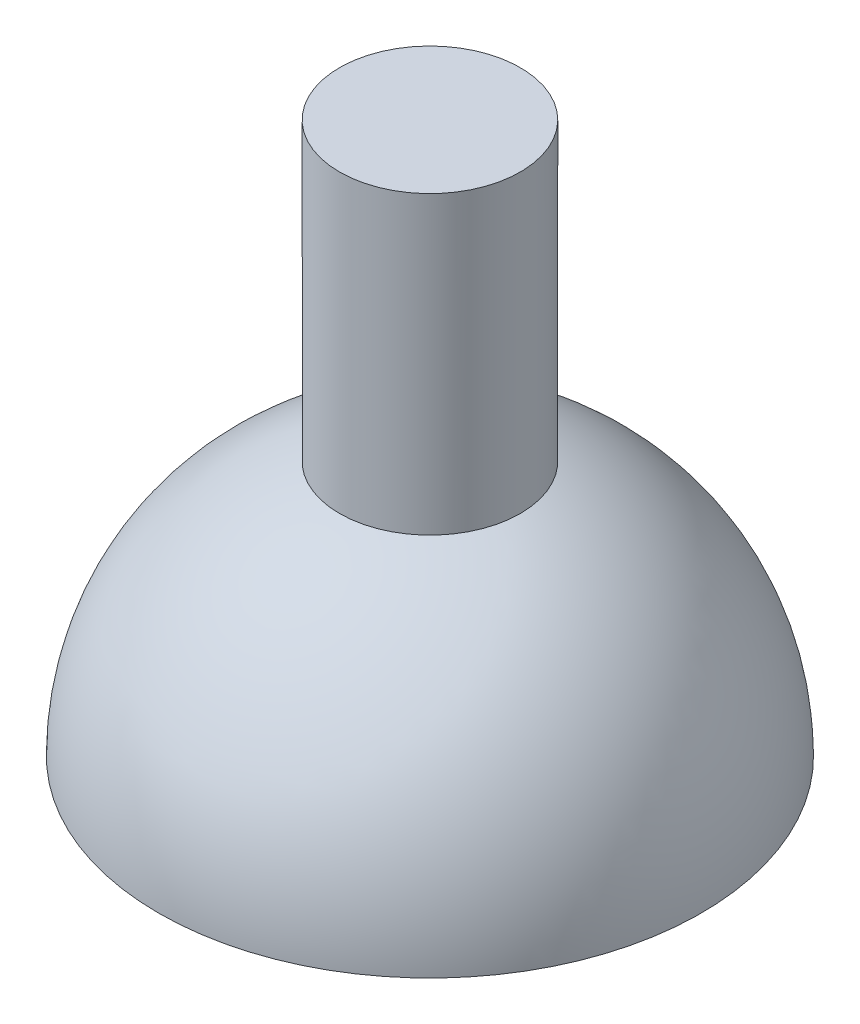
SolidWorks part; units mm, degrees
other "Markup3"
sketch "Sketch4" plane through (-15, 15, 15) normal (-0.0441, 0.9879, 0.1486) x (0.0364, 0.1502, -0.988)
ref_plane "Front Plane" through (0, 0, 0) normal (0, 0, 1) x (1, 0, 0)
ref_plane "Top Plane" through (0, 0, 0) normal (0, 1, 0) x (1, 0, 0)
ref_plane "Right Plane" through (0, 0, 0) normal (1, 0, 0) x (0, 0, -1)
sketch "Sketch5" plane through (0, 0, 0) normal (0, 1, 0) x (1, 0, 0)
  line L0 (0, -30) -> (0, 30)
  arc A0 (0, -30) -> (0, 30) centre (0, 0) ccw
  dimension "D1" = 60
ref_plane "Plane1" through (0, 0, 0) normal (0, 1, 0) x (1, 0, 0)
sketch "Sketch6" plane through (0, 0, 0) normal (0, 1, 0) x (1, 0, 0)
  line L0 (0, -31.7066) -> (0, 32.6478)
revolve "Revolve3" add sketch "Sketch5" angle 360 about L0
ref_plane "Plane2" through (0, 30, 0) normal (0, 1, 0) x (1, 0, 0)
sketch "Sketch7" plane through (0, 30, 0) normal (0, 1, 0) x (1, 0, 0)
  circle A0 centre (0, 0) radius 10
extrude "Boss-Extrude1" add sketch "Sketch7" along normal blind 31 and the other way blind 4 contours A0
sketch "Sketch10" plane through (0, 0, 0) normal (0, 1, 0) x (1, 0, 0)
  circle A0 centre (0, 0) radius 30
extrude "Cut-Extrude1" cut sketch "Sketch10" against normal blind 47 contours A0
shell "Shell1" thickness 1 removed face at (0, 0, 30)
